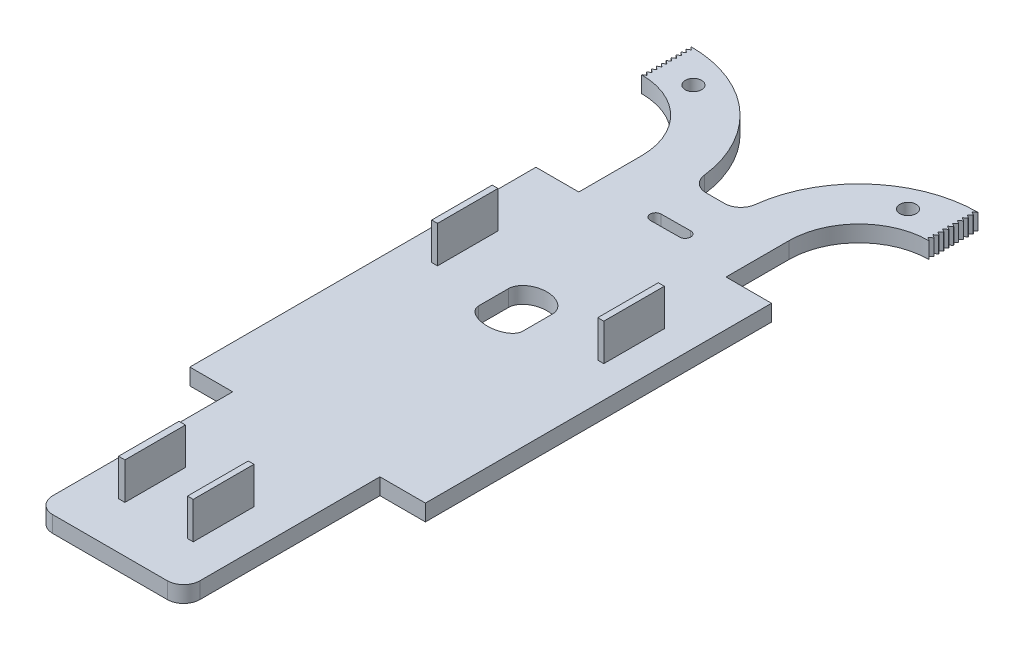
SolidWorks part; units mm, degrees
material "ABS"
ref_plane "Front Plane" through (0, 0, 0) normal (0, 0, 1) x (1, 0, 0)
ref_plane "Top Plane" through (0, 0, 0) normal (0, 1, 0) x (1, 0, 0)
ref_plane "Right Plane" through (0, 0, 0) normal (1, 0, 0) x (0, 0, -1)
sketch "Sketch1" plane through (0, 0, 0) normal (0, 1, 0) x (1, 0, 0)
  line L0 (-74.9602, 156.6268) -> (-74.9602, 156.8096)
  line L1 (-2.1836, 113.8502) -> (27.8164, 113.8502)
  line L2 (-32.1836, 113.8502) -> (-32.1836, -256.1498)
  line L3 (-32.1836, -256.1498) -> (57.8164, -256.1498)
  line L4 (57.8164, 113.8502) -> (57.8164, -256.1498)
  line L5 (-74.9602, 186.6268) -> (-72.9806, 184.9898)
  line L6 (-72.9806, 184.9898) -> (-74.9602, 183.8096)
  line L7 (-74.9602, 183.6268) -> (-72.9806, 181.9898)
  line L8 (-72.9806, 181.9898) -> (-74.9602, 180.8096)
  line L9 (-74.9602, 180.6268) -> (-72.9806, 178.9898)
  line L10 (-72.9806, 178.9898) -> (-74.9602, 177.8096)
  line L11 (-74.9602, 177.6268) -> (-72.9806, 175.9898)
  line L12 (-72.9806, 175.9898) -> (-74.9602, 174.8096)
  line L13 (-74.9602, 174.6268) -> (-72.9806, 172.9898)
  line L14 (-72.9806, 172.9898) -> (-74.9602, 171.8096)
  line L15 (-74.9602, 171.6268) -> (-72.9806, 169.9898)
  line L16 (-72.9806, 169.9898) -> (-74.9602, 168.8096)
  line L17 (-74.9602, 168.6268) -> (-72.9806, 166.9898)
  line L18 (-72.9806, 166.9898) -> (-74.9602, 165.8096)
  line L19 (-74.9602, 165.6268) -> (-72.9806, 163.9898)
  line L20 (-72.9806, 163.9898) -> (-74.9602, 162.8096)
  line L21 (-74.9602, 162.6268) -> (-72.9806, 160.9898)
  line L22 (-72.9806, 160.9898) -> (-74.9602, 159.8096)
  line L23 (-74.9602, 159.6268) -> (-72.9806, 157.9898)
  line L24 (-72.9806, 157.9898) -> (-74.9602, 156.8096)
  line L25 (-74.9602, 183.8096) -> (-74.9602, 183.6268) construction
  line L26 (-74.9602, 183.6268) -> (-74.9602, 183.8096)
  line L27 (-74.9602, 180.6268) -> (-74.9602, 180.8096)
  line L28 (-74.9602, 177.6268) -> (-74.9602, 177.8096)
  line L29 (-74.9602, 174.6268) -> (-74.9602, 174.8096)
  line L30 (-74.9602, 171.6268) -> (-74.9602, 171.8096)
  line L31 (-74.9602, 168.6268) -> (-74.9602, 168.8096)
  line L32 (-74.9602, 165.6268) -> (-74.9602, 165.8096)
  line L33 (-74.9602, 162.6268) -> (-74.9602, 162.8096)
  line L34 (-74.9602, 159.6268) -> (-74.9602, 159.8096)
  line L35 (-2.1836, 113.8502) -> (12.8164, 113.8502)
  line L37 (100.593, 183.8096) -> (100.593, 183.6268) construction
  line L38 (100.593, 159.6268) -> (100.593, 159.8096)
  line L39 (100.593, 162.6268) -> (100.593, 162.8096)
  line L40 (100.593, 165.6268) -> (100.593, 165.8096)
  line L41 (100.593, 168.6268) -> (100.593, 168.8096)
  line L42 (100.593, 171.6268) -> (100.593, 171.8096)
  line L43 (100.593, 174.6268) -> (100.593, 174.8096)
  line L44 (100.593, 177.6268) -> (100.593, 177.8096)
  line L45 (100.593, 180.6268) -> (100.593, 180.8096)
  line L46 (100.593, 183.6268) -> (100.593, 183.8096)
  line L47 (98.6133, 157.9898) -> (100.593, 156.8096)
  line L48 (100.593, 159.6268) -> (98.6133, 157.9898)
  line L49 (98.6133, 160.9898) -> (100.593, 159.8096)
  line L50 (100.593, 162.6268) -> (98.6133, 160.9898)
  line L51 (98.6133, 163.9898) -> (100.593, 162.8096)
  line L52 (100.593, 165.6268) -> (98.6133, 163.9898)
  line L53 (98.6133, 166.9898) -> (100.593, 165.8096)
  line L54 (100.593, 168.6268) -> (98.6133, 166.9898)
  line L55 (98.6133, 169.9898) -> (100.593, 168.8096)
  line L56 (100.593, 171.6268) -> (98.6133, 169.9898)
  line L57 (98.6133, 172.9898) -> (100.593, 171.8096)
  line L58 (100.593, 174.6268) -> (98.6133, 172.9898)
  line L59 (98.6133, 175.9898) -> (100.593, 174.8096)
  line L60 (100.593, 177.6268) -> (98.6133, 175.9898)
  line L61 (98.6133, 178.9898) -> (100.593, 177.8096)
  line L62 (100.593, 180.6268) -> (98.6133, 178.9898)
  line L63 (98.6133, 181.9898) -> (100.593, 180.8096)
  line L64 (100.593, 183.6268) -> (98.6133, 181.9898)
  line L65 (98.6133, 184.9898) -> (100.593, 183.8096)
  line L66 (100.593, 186.6268) -> (98.6133, 184.9898)
  line L67 (100.593, 156.6268) -> (100.593, 156.8096)
  arc A0 (-2.1836, 113.8502) -> (-74.9602, 186.6268) centre (-74.9602, 113.8502) ccw
  arc A1 (-32.1836, 113.8502) -> (-74.9602, 156.6268) centre (-74.9602, 113.8502) ccw
  arc A2 (57.8164, 113.8502) -> (100.593, 156.6268) centre (100.593, 113.8502) cw
  arc A3 (27.8164, 113.8502) -> (100.593, 186.6268) centre (100.593, 113.8502) cw
  dimension "D1" = 10
extrude "Boss-Extrude1" add sketch "Sketch1" along normal blind 10 contours A3 L1 A0 L5 L6 L26 L7 L8 L27 L9 L10 L28 L11 L12 L29 L13 L14 L30 L15 L16 L31 L17 L18 L32 L19 L20 L33 L21 L22 L34 L23 L24 L0 A1 L2 L3 L4 A2 L67 L47 L48 L38 L49 L50 L39 L51 L52 L40 L53 L54 region at (12.8164, 0, 40.1691)
sketch "Sketch9" plane through (0, 10, 0) normal (0, 1, 0) x (1, 0, 0)
  line L0 (-10.4864, -227.6503) -> (-6.5664, -227.6503)
  line L1 (-10.4864, -227.6503) -> (-10.4864, -190.6503)
  line L2 (-10.4864, -190.6503) -> (-6.5664, -190.6503)
  line L3 (-6.5664, -190.6503) -> (-6.5664, -227.6503)
  line L4 (31.6875, -227.6503) -> (31.6875, -190.5238)
  line L5 (31.6875, -190.5238) -> (35.1875, -190.5238)
  line L6 (35.1875, -190.5238) -> (35.1875, -227.6503)
  line L7 (31.6875, -227.6503) -> (35.1875, -227.6503)
  line L8 (-36.2539, -6.9149) -> (-39.7951, -6.9149)
  line L9 (22.5697, 82.3431) -> (4.6643, 82.1832)
  line L10 (22.51, 89.0285) -> (4.6046, 88.8686)
  line L11 (-36.2539, -6.9149) -> (-36.2539, 30.0851)
  line L12 (-36.2539, 30.0851) -> (-39.7951, 30.0851)
  line L13 (-39.7951, -6.9149) -> (-39.7951, 30.0851)
  line L14 (62.6445, -7.8411) -> (66.3345, -7.8411)
  line L15 (62.6445, -7.8411) -> (62.6445, 29.1589)
  line L16 (62.6445, 29.1589) -> (66.3345, 29.1589)
  line L17 (66.3345, -7.8411) -> (66.3345, 29.1589)
  circle A0 centre (-53.7668, 167.0272) radius 5
  arc A1 (22.5697, 82.3431) -> (22.51, 89.0285) centre (22.5399, 85.6858) ccw
  arc A2 (4.6046, 88.8686) -> (4.6643, 82.1832) centre (4.6344, 85.5259) ccw
  circle A3 centre (77.4199, 167.0272) radius 5
extrude "Boss-Extrude5" add sketch "Sketch9" along normal blind 22.5 contours L3 L2 L1 L0 | L4 L7 L6 L5 | L13 L8 L11 L12 | L14 L17 L16 L15 region at (-8.5264, 10, 209.1503) region at (33.4375, 10, 209.087) region at (-38.0245, 10, -11.5851) region at (64.4895, 10, -10.6589)
extrude "Cut-Extrude1" cut sketch "Sketch9<3>" against normal through all both and the other way through all contours L10 A2 L9 A1 | A0 | A3 region at (13.5872, 10, -85.6058)
sketch "Sketch9<3>" plane through (0, 10, 0) normal (0, 1, 0) x (1, 0, 0) same geometry as "Sketch9"
fillet "Fillet1" radius 10 1 edges at (-32.1836, 5, 256.1498) type face fillet first side face at (12.8164, 5, 256.1498) second side face at (-32.1836, 5, 71.1498)
fillet "Fillet2" radius 10 1 edges at (57.8164, 5, 256.1498) type face fillet first side face at (17.8164, 5, 256.1498) second side face at (57.8164, 5, 71.1498)
fillet "Fillet3" radius 10 1 edges at (27.8164, 5, -113.8502) type face fillet first side face at (12.8164, 5, -113.8502) second side face at (56.6684, 5, -157.7747)
fillet "Fillet4" radius 10 1 edges at (-2.1836, 5, -113.8502) type face fillet first side face at (8.1195, 5, -113.8502) second side face at (-31.0357, 5, -157.7747)
sketch "Sketch10" plane through (0, 10, 0) normal (0, 1, 0) x (1, 0, 0)
  line L0 (13.617, 82.2631) -> (13.617, 75.3962) construction
  line L1 (22.5697, 82.3431) -> (4.6643, 82.1832) construction
  line L2 (74.2573, 75.3962) -> (-46.2597, 75.3962) construction
  line L3 (-58.383, 75.3962) -> (85.617, 75.3962)
  line L4 (85.617, 75.3962) -> (85.617, -124.6038)
  line L5 (85.617, -124.6038) -> (13.617, -124.6038)
  line L6 (-58.383, -124.6038) -> (13.617, -124.6038)
  line L7 (-58.383, 75.3962) -> (-58.383, -124.6038)
  dimension "D1" = 72
  dimension "D2" = 200
extrude "Boss-Extrude6" add sketch "Sketch10" against normal blind 10
sketch "Sketch11" plane through (0, 10, 0) normal (0, 1, 0) x (1, 0, 0)
  line L0 (62.8164, -136.1498) -> (92.8164, -136.1498) construction
  line L1 (-58.383, -124.6038) -> (85.617, -124.6038)
  line L2 (-58.383, -124.6038) -> (-58.383, -136.1498)
  line L3 (-58.383, -136.1498) -> (85.617, -136.1498)
  line L4 (85.617, -124.6038) -> (85.617, -136.1498)
extrude "Boss-Extrude7" add sketch "Sketch11" against normal blind 10
sketch "Sketch12" plane through (0, 10, 0) normal (0, 1, 0) x (1, 0, 0)
  line L0 (-2.5271, -15.4638) -> (-2.5271, 2.6987)
  line L1 (24.3642, -15.4638) -> (24.3642, 2.6987)
  ellipse E0 centre (10.9186, 2.6987) end of major axis (24.3642, 2.6987) minor radius 10.0763 (24.3642, 2.6987) -> (-2.5271, 2.6987) ccw
  ellipse E1 centre (10.9186, -15.4638) end of major axis (-2.5271, -15.4638) minor radius 8.077 (-2.5271, -15.4638) -> (24.3642, -15.4638) ccw
  point P14 (0, 0)
  point P15 (0, 0)
  point P16 (0, 0)
  point P17 (0, 0)
  point P18 (0, 0)
  point P19 (0, 0)
  point P20 (0, 0)
  point P21 (0, 0)
  point P22 (0, 0)
extrude "Cut-Extrude2" cut sketch "Sketch12" against normal mid plane 20
